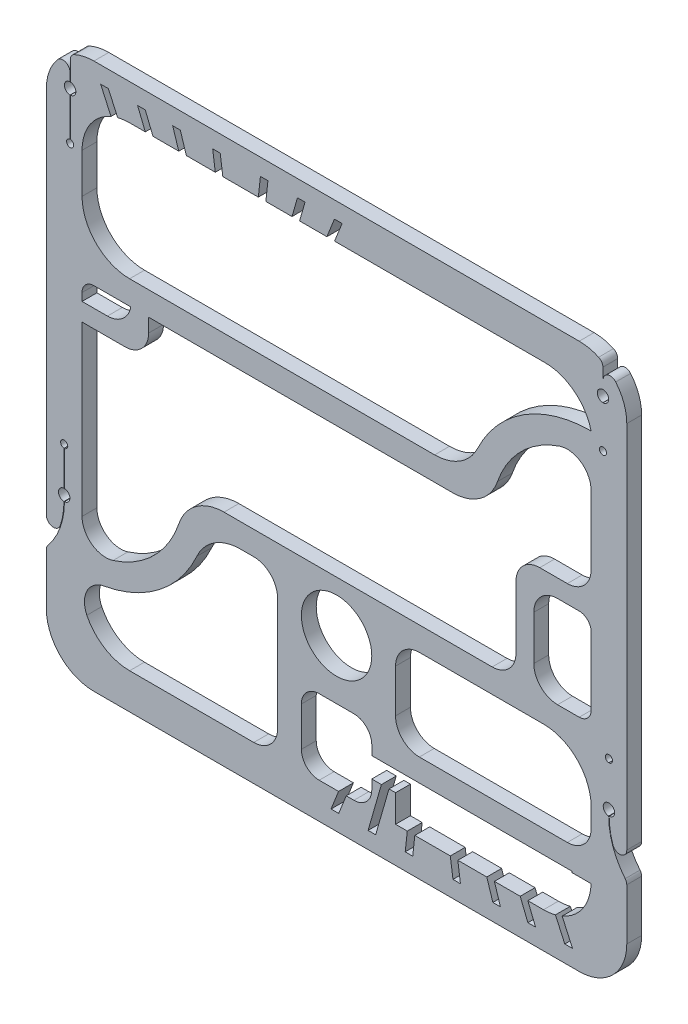
SolidWorks part; units mm, degrees
ref_plane "Front Plane" through (0, 0, 0) normal (0, 0, 1) x (1, 0, 0)
ref_plane "Top Plane" through (0, 0, 0) normal (0, 1, 0) x (1, 0, 0)
ref_plane "Right Plane" through (0, 0, 0) normal (1, 0, 0) x (0, 0, -1)
sketch "Sketch1" plane through (0, 0, 0) normal (0, 0, 1) x (1, 0, 0)
  line L0 (44.642, 21.8842) -> (44.642, 18.0742) construction
  line L1 (-10.1934, 21.8842) -> (51.7832, 21.8842)
  line L2 (-10.1934, 21.8842) -> (-10.1934, -36.406)
  line L3 (-10.1934, -36.406) -> (51.7832, -36.406)
  line L4 (51.7832, 21.8842) -> (51.7832, -36.406)
  line L5 (47.9732, -32.596) -> (-6.3834, -32.596)
  line L6 (47.9732, -32.596) -> (47.9732, 18.0742)
  line L7 (47.9732, 18.0742) -> (-6.3834, 18.0742)
  line L8 (-6.3834, -32.596) -> (-6.3834, 18.0742)
  line L9 (44.642, 19.9792) -> (-35.1587, 19.9792) construction
  line L10 (-6.3834, -31.0517) -> (-10.1934, -31.0517) construction
  line L11 (-8.2884, -31.0517) -> (-8.2884, 6.9585) construction
  line L12 (20.6521, 19.9792) -> (21.1982, 19.9792) construction
  line L14 (3.0779, -32.596) -> (3.0779, -36.406) construction
  line L15 (3.0779, -34.501) -> (37.3423, -34.501) construction
  line L16 (47.9732, -11.8991) -> (47.9732, 12.9942) construction
  line L17 (51.7832, 15.2205) -> (47.9732, 15.2205) construction
  line L18 (49.8782, 15.2205) -> (49.8782, -0.9437) construction
  line L20 (20.9378, -34.501) -> (20.3916, -34.501) construction
  line L21 (-6.3834, 8.0412) -> (-6.3834, -11.8991) construction
  dimension "D1" = 3.81
  dimension "D2" = 3.81
extrude "Boss-Extrude1" add sketch "Sketch1" along normal blind 1.5875
sketch "Sketch2" plane through (0, 0, 0) normal (0, 0, -1) x (-1, 0, 0)
  line L0 (-47.9732, -32.596) -> (-47.9732, 18.0742) construction
  line L1 (-34.8696, 3.653) -> (6.3834, 3.653)
  line L2 (-47.9732, 3.653) -> (-47.9732, 0.8076)
  line L3 (-37.4096, 1.113) -> (6.3834, 1.113)
  line L4 (6.3834, 3.653) -> (6.3834, 1.113)
  line L5 (6.3834, 18.0742) -> (6.3834, -32.596) construction
  line L6 (-33.4496, 1.113) -> (-36.4496, 1.113) construction
  line L7 (1.2504, -12.887) -> (-36.4496, -12.887) construction
  line L8 (-47.9732, -15.427) -> (-6.8239, -15.427)
  line L9 (-47.9732, -15.427) -> (-47.9732, -12.887)
  line L10 (-47.9732, -12.887) -> (-4.5259, -12.887)
  line L11 (1.357, -21.2563) -> (14.2432, -21.2563) construction
  line L12 (6.3834, -23.7963) -> (6.3834, -26.3363)
  line L13 (-47.9732, 14.2166) -> (-47.9732, 11.6766)
  arc A0 (-47.9732, 11.6766) -> (-37.4096, 1.113) centre (-47.9732, 1.113) cw
  arc A1 (-47.9732, 14.2166) -> (-34.8696, 3.653) centre (-47.9732, 0.8076) cw
  arc A2 (6.3834, -23.7963) -> (-4.5259, -12.887) centre (6.3834, -12.887) cw
  arc A3 (-6.8239, -15.427) -> (6.3834, -26.3363) centre (6.3834, -12.887) ccw
  circle A5 centre (1.357, -18.2591) radius 2.9972 construction
  line M5 (-47.9732, -32.596) -> (-47.9732, 18.0742)
  line M7 (6.3834, 18.0742) -> (6.3834, -32.596)
  dimension "D5" = 2.54
  dimension "D1" = 2.54
  dimension "D2" = 2.54
  dimension "D3" = 2.54
  dimension "D4" = 2.54
  dimension "D6" = 2.54
  dimension "D7" = 2.54
extrude "Boss-Extrude2" add sketch "Sketch2" against normal up to surface (1.5875 mm away) contours A1 A0 L3 L1 M5 M7 | L10 L8 M5 M7 region at (14.2431, 3.0939, 0) region at (-5.8234, -25.0663, 0) up to face at (20.7949, -7.2609, 1.5875)
sketch "Sketch3" plane through (0, 0, 0) normal (0, 0, -1) x (-1, 0, 0)
  line L0 (-47.9732, -1.1649) -> (-39.9496, -1.1649)
  line L1 (-47.9732, -12.887) -> (-47.9732, 11.6766) construction
  line L2 (-39.9496, -4.387) -> (-39.9496, -11.387) construction
  line L3 (-39.9496, -1.1649) -> (-39.9496, -12.887)
  line L4 (-47.9732, -12.887) -> (-4.5259, -12.887) construction
  line L5 (-39.9496, -12.887) -> (-41.8546, -12.887)
  line L6 (-41.8546, -12.887) -> (-41.8546, -3.0699)
  line L7 (-41.8546, -3.0699) -> (-47.9732, -3.0699)
  line L8 (-47.9732, -3.0699) -> (-47.9732, -1.1649)
  line L9 (-42.9468, 0.7401) -> (-53.4831, 0.7401) construction
  line L10 (-0.7296, 1.113) -> (-0.7296, -2.887)
  line L11 (-37.4096, 1.113) -> (6.3834, 1.113) construction
  line L12 (-1.9996, -2.887) -> (1.2504, -2.887) construction
  line L13 (-0.7296, -2.887) -> (6.3834, -2.887)
  line L14 (6.3834, 1.113) -> (6.3834, -23.7963) construction
  line L15 (6.3834, -2.887) -> (6.3834, -0.982)
  line L16 (6.3834, -0.982) -> (1.1754, -0.982)
  line L17 (1.1754, -0.982) -> (1.1754, 1.113)
  line L18 (1.1754, 1.113) -> (-0.7296, 1.113)
  circle A0 centre (-42.9468, 3.7373) radius 2.9972 construction
  dimension "D1" = 1.905
  dimension "D2" = 1.905
  dimension "D3" = 1.905
  dimension "D4" = 1.905
  dimension "D5" = 1.27
  dimension "D6" = 1.905
extrude "Boss-Extrude3" add sketch "Sketch3" against normal up to surface (1.5875 mm away) up to face at (20.8645, -5.9566, 1.5875)
fillet "Fillet1" radius 5.08 4 edges at (51.7832, -36.406, 0.7937) (-10.1934, -36.406, 0.7937) (-10.1934, 21.8842, 0.7937) (51.7832, 21.8842, 0.7937)
fillet "Fillet2" radius 5.08 10 edges at (6.8239, -15.427, 0.7937) (47.9732, -15.427, 0.7937) (47.9732, -32.596, 0.7937) (-6.3834, -32.596, 0.7937) (34.8696, 3.653, 0.7938) (-6.3834, 3.653, 0.7937) (47.9732, 18.0742, 0.7937) (-6.3834, 18.0742, 0.7937) (4.5259, -12.887, 0.7937) (37.4096, 1.113, 0.7938)
fillet "Fillet3" radius 2.54 10 edges at (41.8546, -3.0699, 0.7938) (39.9496, -12.887, 0.7938) (41.8546, -12.887, 0.7938) (39.9496, -1.1649, 0.7938) (47.9732, -1.1649, 0.7938) (-1.1754, -0.982, 0.7938) (0.7296, -2.887, 0.7938) (47.9732, 11.6766, 0.7937) (-6.3834, -26.3363, 0.7937) (-6.3834, -23.7963, 0.7937)
fillet "Fillet4" radius 1.27 3 edges at (47.9732, -12.887, 0.7937) (47.9732, -3.0699, 0.7938) (-6.3834, 1.113, 0.7938)
sketch "Sketch5" plane through (0, 0, 0) normal (0, 0, -1) x (-1, 0, 0)
  line L0 (-42.8932, -15.427) -> (-10.5066, -15.427) construction
  line L1 (-27.0941, -15.427) -> (-14.4957, -15.427)
  line L2 (-27.0941, -15.427) -> (-27.0941, -32.596)
  line L3 (-27.0941, -32.596) -> (-14.4957, -32.596)
  line L4 (-14.4957, -15.427) -> (-14.4957, -32.596)
  line L5 (1.3034, -32.596) -> (-42.8932, -32.596) construction
  line L6 (-24.5541, -18.2972) -> (-27.0941, -18.2972) construction
  line L9 (-17.0357, -18.2972) -> (-14.4957, -18.2972) construction
  circle A1 centre (-20.7949, -18.2972) radius 3.7592 construction
  dimension "D1" = 2.54
extrude "Boss-Extrude4" add sketch "Sketch5" against normal up to surface (1.5875 mm away) up to face at (-4.5227, -0.0173, 1.5875)
sketch "Sketch6" plane through (0, 0, 0) normal (0, 0, -1) x (-1, 0, 0)
  circle A0 centre (-20.7949, -18.2972) radius 3.7592 construction
  circle A1 centre (-20.7949, -18.2972) radius 3.7592
extrude "Cut-Extrude2" cut sketch "Sketch6" against normal up to surface (1.5875 mm away) up to face at (4.768, -24.4396, 1.5875)
sketch "Sketch7" plane through (0, 0, 0) normal (0, 0, -1) x (-1, 0, 0)
  line L0 (-27.0941, -15.427) -> (-27.0941, -32.596) construction
  line L1 (-24.5541, -24.5964) -> (-17.0357, -24.5964)
  line L2 (-24.5541, -24.5964) -> (-24.5541, -32.596)
  line L3 (-24.5541, -32.596) -> (-17.0357, -32.596)
  line L4 (-17.0357, -24.5964) -> (-17.0357, -32.596)
  line L5 (-14.4957, -32.596) -> (-14.4957, -15.427) construction
  line L6 (1.3034, -32.596) -> (-14.4957, -32.596) construction
  line L7 (-20.7949, -22.0564) -> (-6.5424, -22.0564) construction
  line L8 (-20.7949, -22.0564) -> (-20.7949, -21.3452) construction
  circle A0 centre (-20.7949, -18.2972) radius 3.7592 construction
  dimension "D1" = 2.54
  dimension "D2" = 2.54
  dimension "D3" = 2.54
extrude "Cut-Extrude3" cut sketch "Sketch7" against normal up to surface (1.5875 mm away) up to face at (24.5541, -18.2972, 1.5875)
fillet "Fillet5" radius 1.905 4 edges at (24.5541, -32.596, 0.7937) (17.0357, -32.596, 0.7938) (17.0357, -24.5964, 0.7938) (24.5541, -24.5964, 0.7938)
sketch "Sketch8" plane through (0, 0, 0) normal (0, 0, -1) x (-1, 0, 0)
  line L0 (-47.9732, -27.516) -> (-47.9732, -20.507) construction
  line L1 (-47.9732, -25.103) -> (-27.0941, -25.103)
  line L2 (-47.9732, -25.103) -> (-47.9732, -27.643)
  line L3 (-47.9732, -27.643) -> (-27.0941, -27.643)
  line L4 (-27.0941, -25.103) -> (-27.0941, -27.643)
  line L5 (-27.0941, -15.427) -> (-27.0941, -32.596) construction
  line L6 (-45.7916, -27.643) -> (-20.3916, -27.643) construction
  dimension "D1" = 2.54
extrude "Boss-Extrude5" add sketch "Sketch8" against normal up to surface (1.5875 mm away) up to face at (20.7949, -28.5962, 1.5875)
fillet "Fillet6" radius 2.54 5 edges at (27.0941, -15.427, 0.7937) (14.4957, -15.427, 0.7937) (14.4957, -32.596, 0.7937) (27.0941, -25.103, 0.7937) (47.9732, -25.103, 0.7937)
sketch "Sketch4" plane through (0, 0, 0) normal (0, 0, -1) x (-1, 0, 0)
  line L0 (3.2504, -2.887) -> (4.7504, -4.387) construction
  line L1 (4.7504, -11.387) -> (3.2504, -12.887) construction
  line L2 (3.2504, -2.887) -> (4.7504, -4.387)
  line L3 (4.7504, -11.387) -> (3.2504, -12.887)
  line L4 (4.7504, -4.387) -> (4.7504, -11.387) construction
  line L5 (4.7504, -4.387) -> (4.7504, -11.387)
  line L6 (3.2504, -2.887) -> (3.2504, -12.887)
  line L32 (4.2018, 13.1212) -> (4.2018, 15.0262)
  line L33 (4.2018, 15.0262) -> (1.9539, 15.0262)
  line L34 (1.9539, 15.0262) -> (4.2018, 19.9792)
  line L35 (4.2018, 19.9792) -> (3.6556, 19.9792)
  line L36 (3.6556, 19.9792) -> (1.4078, 15.0262)
  line L37 (1.4078, 15.0262) -> (-1.7417, 15.0262)
  line L38 (-1.7417, 15.0262) -> (0.2648, 19.9792)
  line L39 (0.2648, 19.9792) -> (-0.2814, 19.9792)
  line L40 (-0.2814, 19.9792) -> (-2.2879, 15.0262)
  line L41 (-2.2879, 15.0262) -> (-5.0437, 15.0262)
  line L42 (-5.0437, 15.0262) -> (-3.469, 19.9792)
  line L43 (-3.469, 19.9792) -> (-4.0152, 19.9792)
  line L44 (-4.0152, 19.9792) -> (-5.5899, 15.0262)
  line L45 (-5.5899, 15.0262) -> (-8.3965, 15.0262)
  line L46 (-8.3965, 15.0262) -> (-7.7108, 19.9792)
  line L47 (-7.7108, 19.9792) -> (-8.257, 19.9792)
  line L48 (-8.257, 19.9792) -> (-8.9427, 15.0262)
  line L49 (-8.9427, 15.0262) -> (-12.2319, 15.0262)
  line L50 (-12.2319, 15.0262) -> (-12.7781, 19.9792)
  line L51 (-12.7781, 19.9792) -> (-13.3242, 19.9792)
  line L52 (-13.3242, 19.9792) -> (-12.7781, 15.0262)
  line L53 (-12.7781, 15.0262) -> (-15.2926, 15.0262)
  line L54 (-15.2926, 15.0262) -> (-16.7151, 19.9792)
  line L55 (-16.7151, 19.9792) -> (-17.2612, 19.9792)
  line L56 (-17.2612, 19.9792) -> (-15.8388, 15.0262)
  line L57 (-15.8388, 15.0262) -> (-18.6963, 15.0262)
  line L58 (-18.6963, 15.0262) -> (-20.6521, 19.9792)
  line L59 (-20.6521, 19.9792) -> (-21.1982, 19.9792)
  line L60 (-21.1982, 19.9792) -> (-19.2425, 15.0262)
  line L61 (-19.2425, 15.0262) -> (-21.1982, 15.0262)
  line L62 (-21.1982, 15.0262) -> (-21.1982, 13.1212)
  line L63 (-21.1982, 13.1212) -> (4.2018, 13.1212)
  line L64 (4.2018, 13.1212) -> (4.2018, 15.0262) construction
  line L65 (4.2018, 15.0262) -> (1.9539, 15.0262) construction
  line L66 (1.9539, 15.0262) -> (4.2018, 19.9792) construction
  line L67 (4.2018, 19.9792) -> (3.6556, 19.9792) construction
  line L68 (3.6556, 19.9792) -> (1.4078, 15.0262) construction
  line L69 (1.4078, 15.0262) -> (-1.7417, 15.0262) construction
  line L70 (-1.7417, 15.0262) -> (0.2648, 19.9792) construction
  line L71 (0.2648, 19.9792) -> (-0.2814, 19.9792) construction
  line L72 (-0.2814, 19.9792) -> (-2.2879, 15.0262) construction
  line L73 (-2.2879, 15.0262) -> (-5.0437, 15.0262) construction
  line L74 (-5.0437, 15.0262) -> (-3.469, 19.9792) construction
  line L75 (-3.469, 19.9792) -> (-4.0152, 19.9792) construction
  line L76 (-4.0152, 19.9792) -> (-5.5899, 15.0262) construction
  line L77 (-5.5899, 15.0262) -> (-8.3965, 15.0262) construction
  line L78 (-8.3965, 15.0262) -> (-7.7108, 19.9792) construction
  line L79 (-7.7108, 19.9792) -> (-8.257, 19.9792) construction
  line L80 (-8.257, 19.9792) -> (-8.9427, 15.0262) construction
  line L81 (-8.9427, 15.0262) -> (-12.2319, 15.0262) construction
  line L82 (-12.2319, 15.0262) -> (-12.7781, 19.9792) construction
  line L83 (-12.7781, 19.9792) -> (-13.3242, 19.9792) construction
  line L84 (-13.3242, 19.9792) -> (-12.7781, 15.0262) construction
  line L85 (-12.7781, 15.0262) -> (-15.2926, 15.0262) construction
  line L86 (-15.2926, 15.0262) -> (-16.7151, 19.9792) construction
  line L87 (-16.7151, 19.9792) -> (-17.2612, 19.9792) construction
  line L88 (-17.2612, 19.9792) -> (-15.8388, 15.0262) construction
  line L89 (-15.8388, 15.0262) -> (-18.6963, 15.0262) construction
  line L90 (-18.6963, 15.0262) -> (-20.6521, 19.9792) construction
  line L91 (-20.6521, 19.9792) -> (-21.1982, 19.9792) construction
  line L92 (-21.1982, 19.9792) -> (-19.2425, 15.0262) construction
  line L93 (-19.2425, 15.0262) -> (-21.1982, 15.0262) construction
  line L94 (-21.1982, 15.0262) -> (-21.1982, 13.1212) construction
  line L95 (-21.1982, 13.1212) -> (4.2018, 13.1212) construction
  line L96 (-45.7916, -27.643) -> (-45.7916, -29.548)
  line L97 (-45.7916, -29.548) -> (-43.5438, -29.548)
  line L98 (-43.5438, -29.548) -> (-45.7916, -34.501)
  line L99 (-45.7916, -34.501) -> (-45.2455, -34.501)
  line L100 (-45.2455, -34.501) -> (-42.9976, -29.548)
  line L101 (-42.9976, -29.548) -> (-39.8482, -29.548)
  line L102 (-39.8482, -29.548) -> (-41.8546, -34.501)
  line L103 (-41.8546, -34.501) -> (-41.3085, -34.501)
  line L104 (-41.3085, -34.501) -> (-39.302, -29.548)
  line L105 (-39.302, -29.548) -> (-36.5462, -29.548)
  line L106 (-36.5462, -29.548) -> (-38.1208, -34.501)
  line L107 (-38.1208, -34.501) -> (-37.5747, -34.501)
  line L108 (-37.5747, -34.501) -> (-36, -29.548)
  line L109 (-36, -29.548) -> (-33.1934, -29.548)
  line L110 (-33.1934, -29.548) -> (-33.879, -34.501)
  line L111 (-33.879, -34.501) -> (-33.3329, -34.501)
  line L112 (-33.3329, -34.501) -> (-32.6472, -29.548)
  line L113 (-32.6472, -29.548) -> (-29.358, -29.548)
  line L114 (-29.358, -29.548) -> (-28.8118, -34.501)
  line L115 (-28.8118, -34.501) -> (-28.2656, -34.501)
  line L116 (-28.2656, -34.501) -> (-28.8118, -29.548)
  line L117 (-28.8118, -29.548) -> (-26.2973, -29.548)
  line L118 (-26.2973, -29.548) -> (-24.8748, -34.501)
  line L119 (-24.8748, -34.501) -> (-24.3286, -34.501)
  line L120 (-24.3286, -34.501) -> (-25.7511, -29.548)
  line L121 (-25.7511, -29.548) -> (-22.8935, -29.548)
  line L122 (-22.8935, -29.548) -> (-20.9378, -34.501)
  line L123 (-20.9378, -34.501) -> (-20.3916, -34.501)
  line L124 (-20.3916, -34.501) -> (-22.3474, -29.548)
  line L125 (-22.3474, -29.548) -> (-20.3916, -29.548)
  line L126 (-20.3916, -29.548) -> (-20.3916, -27.643)
  line L127 (-20.3916, -27.643) -> (-45.7916, -27.643)
  line L128 (-45.7916, -27.643) -> (-45.7916, -29.548) construction
  line L129 (-45.7916, -29.548) -> (-43.5438, -29.548) construction
  line L130 (-43.5438, -29.548) -> (-45.7916, -34.501) construction
  line L131 (-45.7916, -34.501) -> (-45.2455, -34.501) construction
  line L132 (-45.2455, -34.501) -> (-42.9976, -29.548) construction
  line L133 (-42.9976, -29.548) -> (-39.8482, -29.548) construction
  line L134 (-39.8482, -29.548) -> (-41.8546, -34.501) construction
  line L135 (-41.8546, -34.501) -> (-41.3085, -34.501) construction
  line L136 (-41.3085, -34.501) -> (-39.302, -29.548) construction
  line L137 (-39.302, -29.548) -> (-36.5462, -29.548) construction
  line L138 (-36.5462, -29.548) -> (-38.1208, -34.501) construction
  line L139 (-38.1208, -34.501) -> (-37.5747, -34.501) construction
  line L140 (-37.5747, -34.501) -> (-36, -29.548) construction
  line L141 (-36, -29.548) -> (-33.1934, -29.548) construction
  line L142 (-33.1934, -29.548) -> (-33.879, -34.501) construction
  line L143 (-33.879, -34.501) -> (-33.3329, -34.501) construction
  line L144 (-33.3329, -34.501) -> (-32.6472, -29.548) construction
  line L145 (-32.6472, -29.548) -> (-29.358, -29.548) construction
  line L146 (-29.358, -29.548) -> (-28.8118, -34.501) construction
  line L147 (-28.8118, -34.501) -> (-28.2656, -34.501) construction
  line L148 (-28.2656, -34.501) -> (-28.8118, -29.548) construction
  line L149 (-28.8118, -29.548) -> (-26.2973, -29.548) construction
  line L150 (-26.2973, -29.548) -> (-24.8748, -34.501) construction
  line L151 (-24.8748, -34.501) -> (-24.3286, -34.501) construction
  line L152 (-24.3286, -34.501) -> (-25.7511, -29.548) construction
  line L153 (-25.7511, -29.548) -> (-22.8935, -29.548) construction
  line L154 (-22.8935, -29.548) -> (-20.9378, -34.501) construction
  line L155 (-20.9378, -34.501) -> (-20.3916, -34.501) construction
  line L156 (-20.3916, -34.501) -> (-22.3474, -29.548) construction
  line L157 (-22.3474, -29.548) -> (-20.3916, -29.548) construction
  line L158 (-20.3916, -29.548) -> (-20.3916, -27.643) construction
  line L159 (-20.3916, -27.643) -> (-45.7916, -27.643) construction
  line L263 (4.3288, 12.9942) -> (4.3288, 15.1532)
  line L264 (4.3288, 15.1532) -> (2.151, 15.1532)
  line L265 (2.151, 15.1532) -> (4.3989, 20.1062)
  line L266 (4.3989, 20.1062) -> (3.5738, 20.1062)
  line L267 (3.5738, 20.1062) -> (1.3259, 15.1532)
  line L268 (1.3259, 15.1532) -> (-1.5532, 15.1532)
  line L269 (-1.5532, 15.1532) -> (0.4532, 20.1062)
  line L270 (0.4532, 20.1062) -> (-0.367, 20.1062)
  line L271 (-0.367, 20.1062) -> (-2.3735, 15.1532)
  line L272 (-2.3735, 15.1532) -> (-4.8701, 15.1532)
  line L273 (-4.8701, 15.1532) -> (-3.2954, 20.1062)
  line L274 (-3.2954, 20.1062) -> (-4.1081, 20.1062)
  line L275 (-4.1081, 20.1062) -> (-5.6828, 15.1532)
  line L276 (-5.6828, 15.1532) -> (-8.2507, 15.1532)
  line L277 (-8.2507, 15.1532) -> (-7.565, 20.1062)
  line L278 (-7.565, 20.1062) -> (-8.3676, 20.1062)
  line L279 (-8.3676, 20.1062) -> (-9.0533, 15.1532)
  line L280 (-9.0533, 15.1532) -> (-12.1181, 15.1532)
  line L281 (-12.1181, 15.1532) -> (-12.6643, 20.1062)
  line L282 (-12.6643, 20.1062) -> (-13.466, 20.1062)
  line L283 (-13.466, 20.1062) -> (-12.9198, 15.1532)
  line L284 (-12.9198, 15.1532) -> (-15.1969, 15.1532)
  line L285 (-15.1969, 15.1532) -> (-16.6194, 20.1062)
  line L286 (-16.6194, 20.1062) -> (-17.4298, 20.1062)
  line L287 (-17.4298, 20.1062) -> (-16.0074, 15.1532)
  line L288 (-16.0074, 15.1532) -> (-18.6099, 15.1532)
  line L289 (-18.6099, 15.1532) -> (-20.5657, 20.1062)
  line L290 (-20.5657, 20.1062) -> (-21.3849, 20.1062)
  line L291 (-21.3849, 20.1062) -> (-19.4292, 15.1532)
  line L292 (-19.4292, 15.1532) -> (-21.3252, 15.1532)
  line L293 (-21.3252, 15.1532) -> (-21.3252, 12.9942)
  line L294 (-21.3252, 12.9942) -> (4.3288, 12.9942)
  line L295 (-45.9186, -27.516) -> (-45.9186, -29.675)
  line L296 (-45.9186, -29.675) -> (-43.7409, -29.675)
  line L297 (-43.7409, -29.675) -> (-45.9887, -34.628)
  line L298 (-45.9887, -34.628) -> (-45.1636, -34.628)
  line L299 (-45.1636, -34.628) -> (-42.9158, -29.675)
  line L300 (-42.9158, -29.675) -> (-40.0367, -29.675)
  line L301 (-40.0367, -29.675) -> (-42.0431, -34.628)
  line L302 (-42.0431, -34.628) -> (-41.2229, -34.628)
  line L303 (-41.2229, -34.628) -> (-39.2164, -29.675)
  line L304 (-39.2164, -29.675) -> (-36.7198, -29.675)
  line L305 (-36.7198, -29.675) -> (-38.2945, -34.628)
  line L306 (-38.2945, -34.628) -> (-37.4818, -34.628)
  line L307 (-37.4818, -34.628) -> (-35.9071, -29.675)
  line L308 (-35.9071, -29.675) -> (-33.3392, -29.675)
  line L309 (-33.3392, -29.675) -> (-34.0248, -34.628)
  line L310 (-34.0248, -34.628) -> (-33.2222, -34.628)
  line L311 (-33.2222, -34.628) -> (-32.5366, -29.675)
  line L312 (-32.5366, -29.675) -> (-29.4717, -29.675)
  line L313 (-29.4717, -29.675) -> (-28.9256, -34.628)
  line L314 (-28.9256, -34.628) -> (-28.1239, -34.628)
  line L315 (-28.1239, -34.628) -> (-28.67, -29.675)
  line L316 (-28.67, -29.675) -> (-26.3929, -29.675)
  line L317 (-26.3929, -29.675) -> (-24.9705, -34.628)
  line L318 (-24.9705, -34.628) -> (-24.16, -34.628)
  line L319 (-24.16, -34.628) -> (-25.5825, -29.675)
  line L320 (-25.5825, -29.675) -> (-22.9799, -29.675)
  line L321 (-22.9799, -29.675) -> (-21.0242, -34.628)
  line L322 (-21.0242, -34.628) -> (-20.205, -34.628)
  line L323 (-20.205, -34.628) -> (-22.1607, -29.675)
  line L324 (-22.1607, -29.675) -> (-20.2646, -29.675)
  line L325 (-20.2646, -29.675) -> (-20.2646, -27.516)
  line L326 (-20.2646, -27.516) -> (-45.9186, -27.516)
  dimension "D1" = 0
  dimension "D2" = 0
  dimension "D3" = 0.127
  dimension "D4" = 0.127
extrude "Cut-Extrude1" cut sketch "Sketch4" against normal up to surface (1.5875 mm away) up to face at (37.2819, -20.5167, 1.5875)
sketch "Sketch9" plane through (0, 0, 0) normal (0, 0, -1) x (-1, 0, 0)
  circle A0 centre (-49.2432, 18.0742) radius 0.6096 construction
  circle A1 centre (7.6534, 18.0742) radius 0.6096 construction
  circle A2 centre (8.2884, -19.8366) radius 0.6096 construction
  circle A3 centre (-49.8782, -19.8366) radius 0.6096 construction
  circle A4 centre (-49.2432, 18.0742) radius 0.6096
  circle A5 centre (7.6534, 18.0742) radius 0.6096
  circle A6 centre (8.2884, -19.8366) radius 0.6096
  circle A7 centre (-49.8782, -19.8366) radius 0.6096
extrude "Cut-Extrude4" cut sketch "Sketch9" against normal up to surface (1.5875 mm away) up to face at (31.4097, -31.792, 1.5875)
sketch "Sketch10" plane through (0, 0, 1.5875) normal (0, 0, 1) x (1, 0, 0)
  line L0 (-7.6407, 18.6837) -> (-7.6407, 20.7449) construction
  line L1 (-7.6407, 13.375) -> (-7.6407, 17.4647) construction
  line L2 (-7.6661, 17.4647) -> (-7.6661, 13.375) construction
  line L3 (-7.6661, 19.5715) -> (-7.6661, 18.6837) construction
  line L4 (-7.6407, 18.6837) -> (-7.6407, 20.7449)
  line L5 (-7.6407, 13.375) -> (-7.6407, 17.4647)
  line L6 (-7.6661, 17.4647) -> (-7.6661, 13.375)
  line L7 (-7.6661, 19.5715) -> (-7.6661, 18.6837)
  line L8 (49.2305, 18.6837) -> (49.2305, 20.7449) construction
  line L9 (49.2305, 13.375) -> (49.2305, 17.4647) construction
  line L10 (49.2559, 17.4647) -> (49.2559, 13.375) construction
  line L11 (49.2559, 19.5715) -> (49.2559, 18.6837) construction
  line L12 (49.2305, 18.6837) -> (49.2305, 20.7449)
  line L13 (49.2305, 13.375) -> (49.2305, 17.4647)
  line L14 (49.2559, 17.4647) -> (49.2559, 13.375)
  line L15 (49.2559, 19.5715) -> (49.2559, 18.6837)
  line L16 (49.8909, -15.5181) -> (49.8909, -19.2271) construction
  line L17 (49.8655, -15.5181) -> (49.8655, -19.2271) construction
  line L18 (49.8909, -15.5181) -> (49.8909, -19.2271)
  line L19 (49.8655, -15.5181) -> (49.8655, -19.2271)
  line L20 (-8.2757, -15.5181) -> (-8.2757, -19.2271) construction
  line L21 (-8.3011, -15.5181) -> (-8.3011, -19.2271) construction
  line L22 (-8.2757, -15.5181) -> (-8.2757, -19.2271)
  line L23 (-8.3011, -15.5181) -> (-8.3011, -19.2271)
  line L24 (51.7832, -31.326) -> (51.7832, 16.8042) construction
  line L25 (51.7832, -25.8445) -> (51.7832, -22.639)
  line L26 (-10.1934, 16.8042) -> (-10.1934, -31.326) construction
  line L27 (-10.1934, -22.639) -> (-10.1934, -25.8445)
  arc A1 (-7.1902, 21.4403) -> (-7.6407, 20.7449) centre (-6.8787, 20.7449) ccw construction
  arc A2 (-7.6661, 13.375) -> (-7.6407, 13.375) centre (-7.6534, 12.9942) ccw construction
  arc A3 (-7.6661, 19.5715) -> (-9.013, 20.0598) centre (-8.4281, 19.5715) ccw construction
  arc A4 (-5.1134, 21.8842) -> (-10.1934, 16.8042) centre (-5.1134, 16.8042) ccw construction
  arc A5 (-7.1902, 21.4403) -> (-7.6407, 20.7449) centre (-6.8787, 20.7449) ccw
  arc A6 (-7.6661, 13.375) -> (-7.6407, 13.375) centre (-7.6534, 12.9942) ccw
  arc A7 (-7.6661, 19.5715) -> (-9.013, 20.0598) centre (-8.4281, 19.5715) ccw
  arc A8 (-7.1902, 21.4403) -> (-9.013, 20.0598) centre (-5.1134, 16.8042) ccw
  circle A9 centre (-7.6534, 18.0742) radius 0.6096 construction
  arc A10 (-7.6407, 18.6837) -> (-7.6661, 18.6837) centre (-7.6534, 18.0742) ccw
  arc A11 (-7.6661, 17.4647) -> (-7.6407, 17.4647) centre (-7.6534, 18.0742) ccw
  arc A12 (49.2305, 20.7449) -> (48.7801, 21.4403) centre (48.4685, 20.7449) ccw construction
  arc A13 (49.2305, 13.375) -> (49.2559, 13.375) centre (49.2432, 12.9942) ccw construction
  arc A14 (50.6029, 20.0598) -> (49.2559, 19.5715) centre (50.0179, 19.5715) ccw construction
  arc A15 (49.2305, 20.7449) -> (48.7801, 21.4403) centre (48.4685, 20.7449) ccw
  arc A16 (49.2305, 13.375) -> (49.2559, 13.375) centre (49.2432, 12.9942) ccw
  arc A17 (50.6029, 20.0598) -> (49.2559, 19.5715) centre (50.0179, 19.5715) ccw
  arc A18 (49.8909, -15.5181) -> (49.8655, -15.5181) centre (49.8782, -15.1373) ccw construction
  arc A19 (49.9036, -20.4457) -> (50.2983, -22.8798) centre (57.6041, -20.4462) ccw construction
  arc A20 (49.8528, -20.4457) -> (51.6105, -25.3613) centre (57.6041, -20.4462) ccw construction
  arc A21 (50.2983, -22.8798) -> (51.7832, -22.639) centre (51.0212, -22.639) ccw construction
  arc A22 (51.7832, -25.8445) -> (51.6105, -25.3613) centre (51.0212, -25.8445) ccw construction
  arc A23 (49.8909, -15.5181) -> (49.8655, -15.5181) centre (49.8782, -15.1373) ccw
  arc A24 (49.9036, -20.4457) -> (50.2983, -22.8798) centre (57.6041, -20.4462) ccw
  arc A25 (49.8528, -20.4457) -> (51.6105, -25.3613) centre (57.6041, -20.4462) ccw
  arc A26 (50.2983, -22.8798) -> (51.7832, -22.639) centre (51.0212, -22.639) ccw
  arc A27 (51.7832, -25.8445) -> (51.6105, -25.3613) centre (51.0212, -25.8445) ccw
  arc A28 (-10.1934, -22.639) -> (-8.7084, -22.8798) centre (-9.4314, -22.639) ccw construction
  arc A29 (-10.0206, -25.3613) -> (-8.263, -20.4457) centre (-16.0142, -20.4462) ccw construction
  arc A30 (-8.7084, -22.8798) -> (-8.3138, -20.4457) centre (-16.0142, -20.4462) ccw construction
  arc A31 (-8.2757, -15.5181) -> (-8.3011, -15.5181) centre (-8.2884, -15.1373) ccw construction
  arc A32 (-10.1934, -22.639) -> (-8.7084, -22.8798) centre (-9.4314, -22.639) ccw
  arc A33 (-10.0206, -25.3613) -> (-8.263, -20.4457) centre (-16.0142, -20.4462) ccw
  arc A34 (-8.7084, -22.8798) -> (-8.3138, -20.4457) centre (-16.0142, -20.4462) ccw
  arc A35 (-8.2757, -15.5181) -> (-8.3011, -15.5181) centre (-8.2884, -15.1373) ccw
  arc A36 (51.7832, 16.8042) -> (46.7032, 21.8842) centre (46.7032, 16.8042) ccw construction
  arc A37 (50.6029, 20.0598) -> (48.7801, 21.4403) centre (46.7032, 16.8042) ccw
  circle A38 centre (49.2432, 18.0742) radius 0.6096 construction
  arc A39 (49.2559, 18.6837) -> (49.2305, 18.6837) centre (49.2432, 18.0742) ccw
  arc A40 (49.2305, 17.4647) -> (49.2559, 17.4647) centre (49.2432, 18.0742) ccw
  circle A41 centre (49.8782, -19.8366) radius 0.6096 construction
  arc A42 (49.8909, -19.2271) -> (49.8655, -19.2271) centre (49.8782, -19.8366) ccw
  arc A43 (49.8528, -20.4457) -> (49.9036, -20.4457) centre (49.8782, -19.8366) ccw
  circle A44 centre (-8.2884, -19.8366) radius 0.6096 construction
  arc A45 (-8.2757, -19.2271) -> (-8.3011, -19.2271) centre (-8.2884, -19.8366) ccw
  arc A46 (-8.3138, -20.4457) -> (-8.263, -20.4457) centre (-8.2884, -19.8366) ccw
  arc A47 (-10.0206, -25.3613) -> (-10.1934, -25.8445) centre (-9.4314, -25.8445) ccw construction
  arc A48 (-10.0206, -25.3613) -> (-10.1934, -25.8445) centre (-9.4314, -25.8445) ccw
extrude "Slots for carbon" cut sketch "Sketch10" against normal through all
